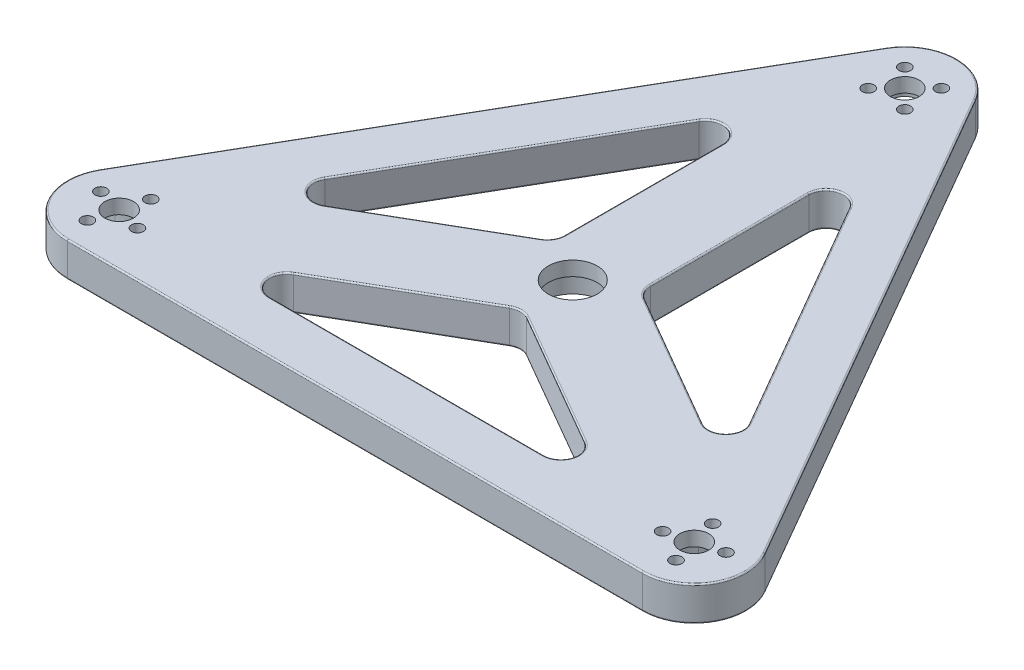
SolidWorks part; units mm, degrees
ref_plane "Front Plane" through (0, 0, 0) normal (0, 0, 1) x (1, 0, 0)
ref_plane "Top Plane" through (0, 0, 0) normal (0, 1, 0) x (1, 0, 0)
ref_plane "Right Plane" through (0, 0, 0) normal (1, 0, 0) x (0, 0, -1)
sketch "Sketch1" plane through (0, 0, 0) normal (0, 1, 0) x (1, 0, 0)
  line L0 (-15.5885, 124.4701) -> (-115.5885, -48.735)
  line L1 (-100, -75.735) -> (100, -75.735)
  line L2 (115.5885, -48.735) -> (15.5885, 124.4701)
  line L3 (0, 115.4701) -> (0, 0) construction
  line L4 (0, 0) -> (-100, -57.735) construction
  line L5 (0, 0) -> (100, -57.735) construction
  line L6 (0, 115.4701) -> (-100, -57.735) construction
  line L7 (-100, -57.735) -> (100, -57.735) construction
  line L8 (100, -57.735) -> (0, 115.4701) construction
  line L9 (-15, 89.4893) -> (-85, -31.7543)
  line L10 (-85, -31.7543) -> (-15, 8.6603)
  line L11 (-15, 8.6603) -> (-15, 89.4893)
  line L12 (15, 89.4893) -> (85, -31.7543)
  line L13 (85, -31.7543) -> (15, 8.6603)
  line L14 (15, 8.6603) -> (15, 89.4893)
  line L15 (-70, -57.735) -> (70, -57.735)
  line L16 (70, -57.735) -> (0, -17.3205)
  line L17 (0, -17.3205) -> (-70, -57.735)
  line L18 (-15, 8.6603) -> (0, 0) construction
  line L19 (15, 8.6603) -> (0, 0) construction
  line L20 (0, 0) -> (0, -17.3205) construction
  line L21 (6.364, 121.834) -> (0, 115.4701) construction
  line L22 (0, 115.4701) -> (-6.364, 109.1061) construction
  line L23 (-6.364, 121.834) -> (0, 115.4701) construction
  line L24 (0, 115.4701) -> (6.364, 109.1061) construction
  line L25 (8.814, 121.834) -> (8.814, 109.1061) construction
  line L27 (-1, 110.5711) -> (-1, 106.5775)
  line L28 (1, 110.5711) -> (1, 106.5775)
  line L29 (97.6706, -49.0417) -> (100, -57.735) construction
  line L30 (100, -57.735) -> (102.3294, -66.4284) construction
  line L31 (91.3067, -60.0644) -> (100, -57.735) construction
  line L32 (100, -57.735) -> (108.6933, -55.4057) construction
  line L33 (98.8956, -46.9199) -> (109.9183, -53.2839) construction
  line L34 (-97.6706, -49.0417) -> (-100, -57.735) construction
  line L35 (-100, -57.735) -> (-102.3294, -66.4284) construction
  line L36 (-108.6933, -55.4057) -> (-100, -57.735) construction
  line L37 (-100, -57.735) -> (-91.3067, -60.0644) construction
  line L38 (-95.5489, -47.8167) -> (-89.1849, -58.8394) construction
  circle A0 centre (0, 0) radius 8.5
  circle A1 centre (0, 115.4701) radius 5
  circle A2 centre (100, -57.735) radius 5
  arc A4 (15.5885, 124.4701) -> (-15.5885, 124.4701) centre (0, 115.4701) ccw
  arc A5 (-100, -75.735) -> (-115.5885, -48.735) centre (-100, -57.735) cw
  arc A6 (115.5885, -48.735) -> (100, -75.735) centre (100, -57.735) cw
  circle A7 centre (0, 0) radius 11
  circle A11 centre (-6.364, 121.834) radius 2.45
  circle A12 centre (6.364, 121.834) radius 2.45
  circle A13 centre (-6.364, 109.1061) radius 2.45
  circle A14 centre (6.364, 109.1061) radius 2.45
  arc A15 (-3.7374, 125.4879) -> (-10.0179, 119.2074) centre (-6.364, 121.834) ccw
  arc A16 (10.0179, 119.2074) -> (3.7374, 125.4879) centre (6.364, 121.834) ccw
  arc A17 (3.7374, 105.4522) -> (10.0179, 111.7327) centre (6.364, 109.1061) ccw
  arc A18 (-10.0179, 111.7327) -> (-3.7374, 105.4522) centre (-6.364, 109.1061) ccw
  arc A19 (-10.0179, 119.2074) -> (-10.0179, 111.7327) centre (-15.217, 115.4701) cw
  arc A20 (-3.7374, 125.4879) -> (3.7374, 125.4879) centre (0, 130.6871) ccw
  arc A21 (10.0179, 119.2074) -> (10.0179, 111.7327) centre (15.217, 115.4701) ccw
  arc A22 (3.7374, 105.4522) -> (-3.7374, 105.4522) centre (0, 100.253) ccw
  circle A23 centre (-6.364, 121.834) radius 2.05
  circle A24 centre (-6.364, 109.1061) radius 2.05
  circle A25 centre (6.364, 109.1061) radius 2.05
  circle A26 centre (6.364, 121.834) radius 2.05
  circle A27 centre (100, -57.735) radius 5
  circle A28 centre (-100, -57.735) radius 5
  circle A29 centre (91.3067, -60.0644) radius 2.45
  circle A30 centre (97.6706, -49.0417) radius 2.45
  circle A31 centre (102.3294, -66.4284) radius 2.45
  circle A32 centre (108.6933, -55.4057) radius 2.45
  arc A33 (89.4556, -55.9628) -> (91.7544, -64.5421) centre (91.3067, -60.0644) ccw
  arc A34 (101.7723, -47.1906) -> (93.193, -49.4894) centre (97.6706, -49.0417) ccw
  arc A35 (110.5444, -59.5073) -> (108.2456, -50.928) centre (108.6933, -55.4057) ccw
  arc A36 (98.2277, -68.2794) -> (106.807, -65.9806) centre (102.3294, -66.4284) ccw
  arc A37 (91.7544, -64.5421) -> (98.2277, -68.2794) centre (92.3915, -70.9133) cw
  arc A38 (89.4556, -55.9628) -> (93.193, -49.4894) centre (86.8217, -50.1265) ccw
  arc A39 (101.7723, -47.1906) -> (108.2456, -50.928) centre (107.6085, -44.5567) ccw
  arc A40 (110.5444, -59.5073) -> (106.807, -65.9806) centre (113.1783, -65.3435) ccw
  circle A41 centre (91.3067, -60.0644) radius 2.05
  circle A42 centre (102.3294, -66.4284) radius 2.05
  circle A43 centre (108.6933, -55.4057) radius 2.05
  circle A44 centre (97.6706, -49.0417) radius 2.05
  circle A46 centre (-108.6933, -55.4057) radius 2.45
  circle A47 centre (-97.6706, -49.0417) radius 2.45
  circle A48 centre (-102.3294, -66.4284) radius 2.45
  circle A49 centre (-91.3067, -60.0644) radius 2.45
  arc A50 (-108.2456, -50.928) -> (-110.5444, -59.5073) centre (-108.6933, -55.4057) ccw
  arc A51 (-93.193, -49.4894) -> (-101.7723, -47.1906) centre (-97.6706, -49.0417) ccw
  arc A52 (-91.7544, -64.5421) -> (-89.4556, -55.9628) centre (-91.3067, -60.0644) ccw
  arc A53 (-106.807, -65.9806) -> (-98.2277, -68.2794) centre (-102.3294, -66.4284) ccw
  arc A54 (-110.5444, -59.5073) -> (-106.807, -65.9806) centre (-113.1783, -65.3435) cw
  arc A55 (-108.2456, -50.928) -> (-101.7723, -47.1906) centre (-107.6085, -44.5567) ccw
  arc A56 (-93.193, -49.4894) -> (-89.4556, -55.9628) centre (-86.8217, -50.1265) ccw
  arc A57 (-91.7544, -64.5421) -> (-98.2277, -68.2794) centre (-92.3915, -70.9133) ccw
  circle A58 centre (-108.6933, -55.4057) radius 2.05
  circle A59 centre (-102.3294, -66.4284) radius 2.05
  circle A60 centre (-91.3067, -60.0644) radius 2.05
  circle A61 centre (-97.6706, -49.0417) radius 2.05
  point P81 (-100.3762, -57.735)
  dimension "D1" = 10
  dimension "D2" = 17
  dimension "D3" = 22
  dimension "D4" = 18
  dimension "D7" = 4.9
  dimension "D8" = 4.5
  dimension "D11" = 4.1
  dimension "D5" = 200
  dimension "D6" = 140
  dimension "D9" = 9
  dimension "D10" = 2
extrude "Boss-Extrude1" add sketch "Sketch1" along normal blind 12 contours A6 L2 A4 L0 A5 L1 A35 A40 A36 A37 A33 A38 A34 A39 L13 L14 L12 L11 L10 L9 L17 L16 L15 A7 A17 A22 A18 A19 A15 A20 A16 A21 A52 A57 A53 A54 A50 A55 A51 A56 | A57 A52 A56 A51 A55 A50 A54 A53 A49 A48 A47 A46 A28 | A46 A58 | A48 A59 | A49 A60 | A47 A61 | A40 A35 A39 A34 A38 A33 A37 A36 A32 A31 A30 A29 A2 | A30 A44 | A32 A43 | A31 A42 | A29 A41 | A22 A17 A21 A16 A20 A15 A19 A18 L27 A1 L28 A14 A13 A12 A11 | A11 A23 | A12 A26 | A14 A25 | A22 L28 A1 L27 | A13 A24 | A7 A0 region at (0, 0, -130.3163) region at (0, 0, -108.5668) region at (-1.3073, 0, -108.5743) region at (-10.6889, 0, 0) region at (-8.7447, 0, -121.834) region at (3.9833, 0, -121.834) region at (-8.7447, 0, -109.1061) region at (3.9833, 0, -109.1061) region at (88.926, 0, 60.0644) region at (95.2899, 0, 49.0417) region at (99.9487, 0, 66.4284) region at (106.3126, 0, 55.4057) region at (92.6901, 0, 53.5146) region at (-111.074, 0, 55.4057) region at (-100.0513, 0, 49.0417) region at (-104.7101, 0, 66.4284) region at (-93.6874, 0, 60.0644) region at (-104.2204, 0, 50.4251)
extrude "Cut-Extrude1" cut sketch "Sketch1<3>" along normal blind 7 contours A7 A0 | A57 A52 A56 A51 A55 A50 A54 A53 A49 A48 A47 A46 A28 | A48 A59 | A49 A60 | A47 A61 | A46 A58 | A22 A17 A21 A16 A20 A15 A19 A18 L27 A1 L28 A14 A13 A12 A11 | A12 A26 | A11 A23 | A13 A24 | A22 L28 A1 L27 | A14 A25 | A40 A35 A39 A34 A38 A33 A37 A36 A32 A31 A30 A29 A2 | A32 A43 | A31 A42 | A29 A41 | A30 A44 region at (0, 0, -108.5668) region at (-1.3073, 0, -108.5743) region at (-10.6889, 0, 0) region at (-8.7447, 0, -121.834) region at (3.9833, 0, -121.834) region at (-8.7447, 0, -109.1061) region at (3.9833, 0, -109.1061) region at (88.926, 0, 60.0644) region at (95.2899, 0, 49.0417) region at (99.9487, 0, 66.4284) region at (106.3126, 0, 55.4057) region at (92.6901, 0, 53.5146) region at (-111.074, 0, 55.4057) region at (-100.0513, 0, 49.0417) region at (-104.7101, 0, 66.4284) region at (-93.6874, 0, 60.0644) region at (-104.2204, 0, 50.4251)
sketch "Sketch1<3>" plane through (0, 0, 0) normal (0, 1, 0) x (1, 0, 0) same geometry as "Sketch1"
fillet "Fillet1" radius 6 9 edges at (70, 6, 57.735) (85, 6, 31.7543) (-15, 6, -8.6603) (-85, 6, 31.7543) (-70, 6, 57.735) (15, 6, -8.6603) (15, 6, -89.4893) (-15, 6, -89.4893) (0, 6, 17.3205)
fillet "Fillet2" radius 0.5 48 edges at (0, 0, 18.2487) (26.8038, 0, 32.7957) (53.4033, 0, 53.2879) (0, 0, 57.735) (-53.4033, 0, 53.2879) (0, 12, 18.2487) (26.8038, 12, 32.7957) (53.4033, 12, 53.2879) (0, 12, 57.735) (-53.4033, 12, 53.2879) (-19.4471, 12, -72.8925) (-15, 12, -39.6107) (-15.8038, 12, -9.1244) (-41.8038, 12, 6.815) (-72.8503, 12, 19.6046) (-72.8503, 0, 19.6046) (-50, 0, -28.8675) (-19.4471, 0, -72.8925) (-15, 0, -39.6107) (-15.8038, 0, -9.1244) (72.8503, 12, 19.6046) (50, 12, -28.8675) (19.4471, 12, -72.8925) (15, 12, -39.6107) (15.8038, 12, -9.1244) (72.8503, 0, 19.6046) (50, 0, -28.8675) (19.4471, 0, -72.8925) (15, 0, -39.6107) (15.8038, 0, -9.1244) (115.5885, 12, 66.735) (0, 12, 75.735) (-115.5885, 12, 66.735) (-65.5885, 12, -37.8675) (0, 12, -133.4701) (115.5885, 0, 66.735) (0, 0, 75.735) (-115.5885, 0, 66.735) (-65.5885, 0, -37.8675) (0, 0, -133.4701) (-26.8038, 0, 32.7957) (-26.8038, 12, 32.7957) (-50, 12, -28.8675) (-41.8038, 0, 6.815) (41.8038, 12, 6.815) (41.8038, 0, 6.815) (65.5885, 12, -37.8675) (65.5885, 0, -37.8675)
